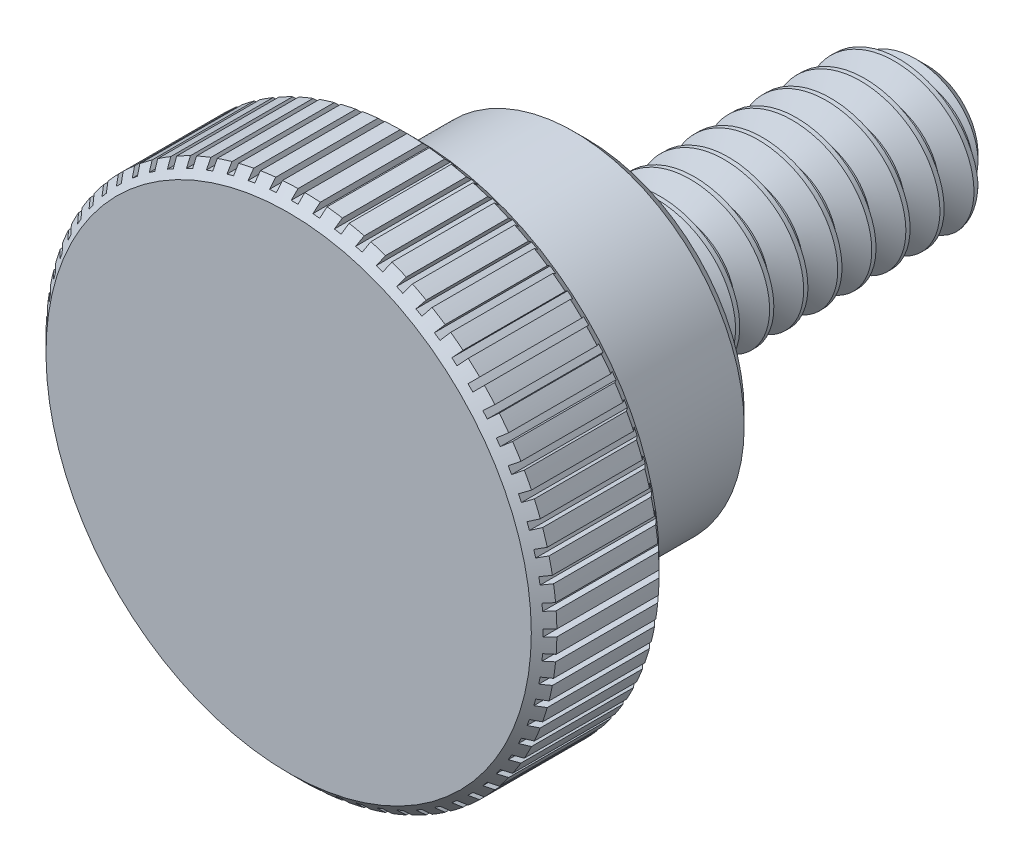
SolidWorks part; units mm, degrees
ref_plane "Front" through (0, 0, 0) normal (0, 0, 1) x (1, 0, 0)
ref_plane "Top" through (0, 0, 0) normal (0, 1, 0) x (1, 0, 0)
ref_plane "Right" through (0, 0, 0) normal (1, 0, 0) x (0, 0, -1)
sketch "Sketch20" plane through (0, 0, 0) normal (1, 0, 0) x (0, 0, -1)
  line L0 (0, 0) -> (6.35, 0) construction
  line L1 (6.35, 1.4224) -> (6.35, -1.4224) construction
  line L2 (-3.175, 4.7625) -> (-3.175, -4.7625) construction
  line L3 (-5.5562, 4.7625) -> (-5.5562, -4.7625) construction
  line L4 (0, 3.175) -> (0, -3.175) construction
  point P9 (3.4925, -1.4224)
  point P11 (-3.175, 0)
  point P14 (0, 0)
  dimension "D1" = 2.8448
  dimension "D2" = 6.35
  dimension "D3" = 2.8575
  dimension "Shoulder Diameter" = 6.35
  dimension "Shoulder Length" = 3.175
  dimension "Head Diameter" = 9.525
  dimension "Head Height" = 2.3813
sketch "Sketch1" plane through (0, 0, 0) normal (0, 0, 1) x (1, 0, 0)
  circle A0 centre (0, 0) radius 1.4224
  dimension "dia" = 2.8448
extrude "Extrude1" add sketch "Sketch1" against normal blind 6.35
chamfer "Chamfer2" distance 0.4763 angle 45 1 edges at (1.4224, 0, -6.35)
sketch "Sketch15" plane through (0, 0, -6.35) normal (0, 0, -1) x (-1, 0, 0)
  circle A0 centre (0, 0) radius 1.4224 construction
  circle A2 centre (0, 0) radius 1.4224
curve "Helix/Spiral1" pitch 0.635 height 6.985 radius 1.4224 centre (0, 0, -6.35) axis (0, 0, 1) start towards (0, 1, 0) parameters "pitch"=0.635
sketch "Sketch14" plane through (0, 0, 0) normal (1, 0, 0) x (0, 0, -1)
  line L0 (6.35, 1.4224) -> (6.9056, 1.4224)
  line L1 (6.9056, 1.4224) -> (6.6675, 1.01)
  line L2 (6.6675, 1.01) -> (6.5881, 1.01)
  line L3 (6.5881, 1.01) -> (6.35, 1.4224)
  line L4 (6.4691, 1.2162) -> (6.7866, 1.2162) construction
  line L5 (6.35, -1.4224) -> (6.35, 1.4224) construction
  dimension "D1" = 0.0794
  dimension "D2" = 0.3175
  dimension "D3" = 60
sweep "Cut-Sweep1" cut profiles "Sketch14" path "Helix/Spiral1" align with end faces yes
sketch "Sketch27" plane through (0, 0, 0) normal (0, 0, 1) x (1, 0, 0)
  circle A0 centre (0, 0) radius 3.175
extrude "Boss-Extrude4" add sketch "Sketch27" along normal up to vertex (3.175 mm away) up to point (0, 0, 3.175)
sketch "Sketch21" plane through (0, 0, 3.175) normal (0, 0, 1) x (1, 0, 0)
  line L0 (-4.7625, 0) -> (4.7625, 0) construction
  circle A0 centre (0, 0) radius 4.7625
extrude "Boss-Extrude1" add sketch "Sketch21" along normal up to vertex (2.3813 mm away) up to point (0, -4.7625, 5.5562)
chamfer "Chamfer3" distance 0.2381 angle 45 3 edges at (4.7625, 0, 3.175) (4.7625, 0, 5.5562) (3.175, 0, 0)
fillet "Fillet1" radius 0.2381 1 edges at (3.175, 0, 3.175)
ref_plane "Plane1" through (0, 4.7625, 0) normal (0, 1, 0) x (-1, 0, 0)
sketch "Sketch22" plane through (0, 4.7625, 0) normal (0, 1, 0) x (-1, 0, 0)
  line L0 (0, 5.5562) -> (0, 3.175) construction
  line L1 (-0.0635, 5.5562) -> (0.0635, 5.5562)
  line L3 (-0.0635, 5.5562) -> (-0.0635, 3.175)
  line L4 (-0.0635, 3.175) -> (0.0635, 3.175)
  line L7 (0.0635, 5.5562) -> (0.0635, 3.175)
  dimension "D1" = 0.127
extrude "Cut-Extrude1" cut sketch "Sketch22" against normal offset from surface (0.1274 mm away) 0.127 up to face at (4.7625, 0, 3.4131) offset beyond the face yes
pattern_circular "CirPattern1" count 72 over 360 about axis through (0, 0, 5.5562) along (0, 0, -1) of "Cut-Extrude1"
equation "\"D3@Helix/Spiral1\" = \"Lg@Extrude1\"+\"pitch@Helix/Spiral1\""
equation "\"D1@Sketch14\" = \"pitch@Helix/Spiral1\" * .125"
equation "\"D2@Sketch14\" = \"pitch@Helix/Spiral1\" * .5"
equation "\"D1@Chamfer2\" = \"pitch@Helix/Spiral1\" * .75"
equation "\"D1@Sketch20\" = \"dia@Sketch1\""
equation "\"D2@Sketch20\" = \"Lg@Extrude1\""
equation "\"D1@Chamfer3\" =\"Head Height@Sketch20\"/10"
equation "\"D3@Sketch20\" = \"pitch@Helix/Spiral1\"*4.50"
equation "\"D1@Fillet1\" = \"D1@Chamfer3\""
